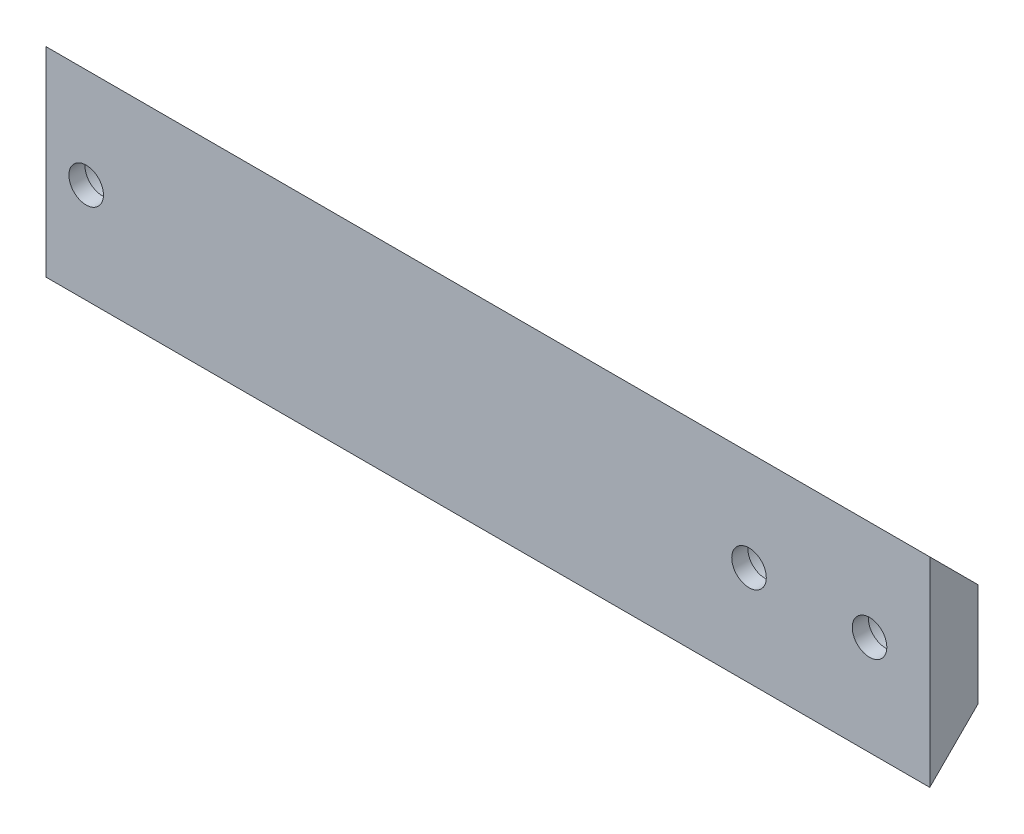
SolidWorks part; units mm, degrees
ref_plane "Front Plane" through (0, 0, 0) normal (0, 0, 1) x (1, 0, 0)
ref_plane "Top Plane" through (0, 0, 0) normal (0, 1, 0) x (1, 0, 0)
ref_plane "Right Plane" through (0, 0, 0) normal (1, 0, 0) x (0, 0, -1)
sketch "Sketch1" plane through (0, 0, 0) normal (0, 0, 1) x (1, 0, 0)
  line L1 (-55, 12.425) -> (55, 12.425)
  line L2 (-55, 12.425) -> (-55, -12.425)
  line L3 (-55, -12.425) -> (55, -12.425)
  line L4 (55, 12.425) -> (55, -12.425)
  line L5 (-55, 12.425) -> (55, -12.425) construction
  line L6 (-55, -12.425) -> (55, 12.425) construction
  point P0 (0, 0)
  dimension "D1" = 24.85
  dimension "D2" = 110
extrude "Boss-Extrude1" add sketch "Sketch1" along normal blind 6
chamfer "Chamfer1" distance 6 angle 45 2 edges at (0, -12.425, 0) (0, 12.425, 0)
hole_wizard "CBORE for M4 SHCS1" positions "Sketch4" profile "Sketch5" counterbore size "M4" standard "ANSI Metric"
sketch "Sketch4" plane through (0, 0, 0) normal (0, 0, -1) x (-1, 0, 0)
  line L0 (-55, 0) -> (-47.5, 0) construction
  line L1 (-55, -6.425) -> (-55, 6.425) construction
  line L2 (-47.5, 0) -> (-40, 0) construction
  line L3 (-40, 0) -> (-32.5, 0) construction
  line L4 (-32.5, 0) -> (-25, 0) construction
  line L5 (55, 6.425) -> (55, -6.425) construction
  point P0 (-47.5, 0)
  point P2 (-32.5, 0)
  point P18 (50, 0)
  point P23 (0, 0)
  dimension "D1" = 30
  dimension "D2" = 5
sketch "Sketch5" plane through (47.5, 0, 0) normal (1, 0, 0) x (0, 1, 0)
  line L0 (0, 0) -> (0, 11.3919)
  line L1 (0, 11.3919) -> (2.15, 10.1)
  line L2 (2.15, 10.1) -> (2.15, 4)
  line L3 (2.15, 4) -> (4, 4)
  line L4 (4, 4) -> (4, 0)
  line L5 (4, 0) -> (0, 0)
  line L10 (0, 11.3919) -> (-2.15, 10.1) construction
  line L11 (0, -6.35) -> (0, 107.95) construction
  dimension "Hole Dia." = 4.3
  dimension "Hole Depth" = 10.1
  dimension "C'Bore Dia." = 8
  dimension "C'Bore Depth" = 4
  dimension "Drill Angle" = 118
